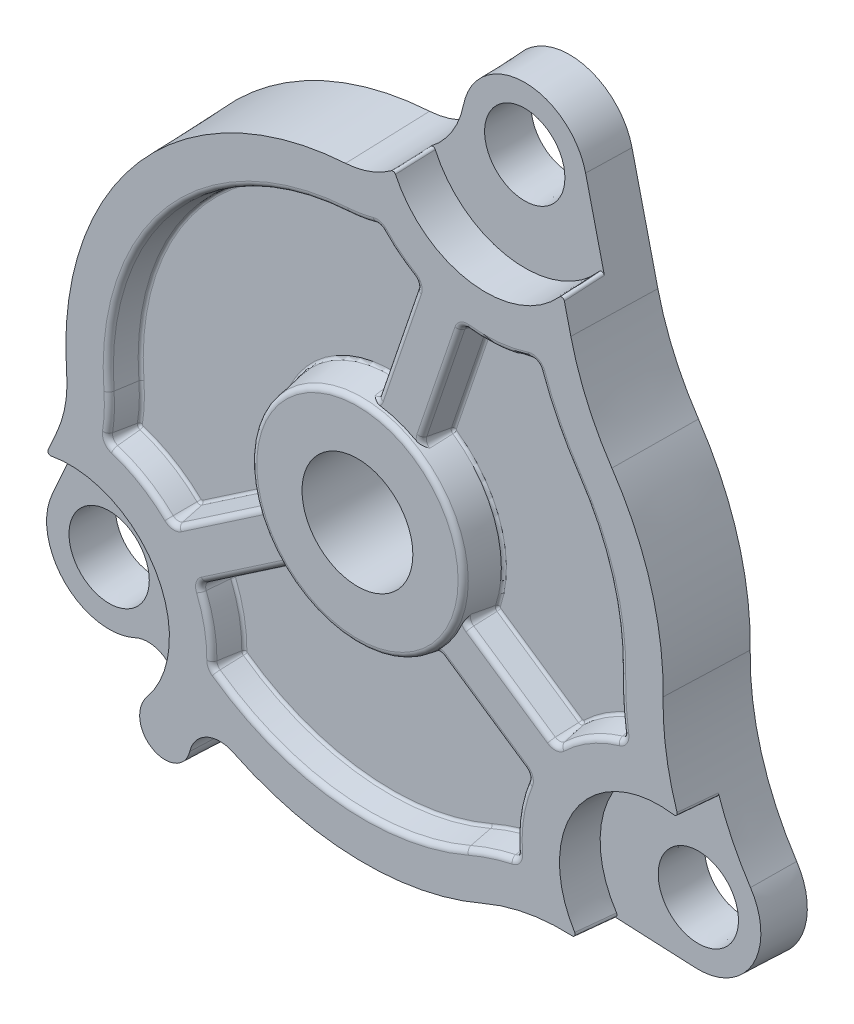
SolidWorks part; units mm, degrees
material "7075-T6 (SN)"
ref_plane "Plane1" through (0, 0, 0) normal (0, 0, 1) x (1, 0, 0)
ref_plane "Plane2" through (0, 0, 0) normal (0, 1, 0) x (-1, 0, 0)
ref_plane "Plane3" through (0, 0, 0) normal (1, 0, 0) x (0, 0, -1)
sketch "Sketch1" plane through (0, 0, 0) normal (0, 0, 1) x (1, 0, 0)
  line L0 (-26.67, -18.1463) -> (26.67, -18.1463) construction
  line L1 (0, 0) -> (-26.67, -18.1463) construction
  line L2 (0, 0) -> (26.67, -18.1463) construction
  line L3 (10.9563, 32.2244) -> (0, 0) construction
  line L4 (16.6043, 33.5606) -> (18.9435, 23.6736)
  line L6 (18.789, -23.5906) -> (26.4008, -23.944)
  line L11 (-28.0689, -6.9945) -> (-31.9746, -15.7912)
  line L12 (-18.0518, -25.6544) -> (0, 0) construction
  arc A1 (-31.9746, -15.7912) -> (-24.2263, -23.4107) centre (-26.67, -18.1463) ccw
  arc A3 (16.6043, 33.5606) -> (5.2649, 33.3618) centre (10.9563, 32.2244) ccw
  arc A4 (27.3007, -0.4835) -> (22.6196, 15.2943) centre (0, 0) ccw
  arc A5 (31.511, -14.9447) -> (27.3007, -0.4835) centre (52.6967, -0.9332) cw
  arc A6 (5.2649, 33.3618) -> (-1.7257, 27.2504) centre (-2.2073, 34.8552) cw
  arc A7 (-1.7257, 27.2504) -> (-27.2247, -2.0929) centre (0, 0) ccw
  arc A9 (26.4008, -23.944) -> (31.511, -14.9447) centre (26.67, -18.1463) ccw
  arc A10 (-11.969, -24.5419) -> (10.8798, -25.0438) centre (0, 0) ccw
  arc A12 (-27.2247, -2.0929) -> (-28.0689, -6.9945) centre (-37.3548, -2.8716) cw
  arc A13 (22.6196, 15.2943) -> (18.9435, 23.6736) centre (43.6611, 29.5216) cw
  arc A14 (18.789, -23.5906) -> (10.8798, -25.0438) centre (17.9643, -41.3514) ccw
  arc A15 (-20.617, -25.6846) -> (-15.5547, -26.2426) centre (-18.0518, -25.6544) ccw
  arc A16 (-11.969, -24.5419) -> (-15.5547, -26.2426) centre (-13.0824, -26.8249) ccw
  arc A17 (-20.617, -25.6846) -> (-24.2263, -23.4107) centre (-23.1568, -25.7146) ccw
  circle A18 centre (10.9563, 32.2244) radius 3.4925
  circle A19 centre (-26.67, -18.1463) radius 3.4925
  circle A20 centre (26.67, -18.1463) radius 3.4925
  dimension "D1" = 54.61
  dimension "D2" = 53.34
  dimension "D3" = 11.6078
  dimension "D4" = 32.258
  dimension "D8" = 10.16
  dimension "D9" = 7.62
  dimension "D10" = 25.4
  dimension "D11" = 17.78
  dimension "D14" = 2.54
  dimension "D16" = 2.5654
  dimension "D20" = 6.985
  dimension "D5" = 34.036
  dimension "D6" = 105.453
  dimension "D12" = 10.16
  dimension "D13" = 7.62
  dimension "D17" = 31.369
  dimension "D18" = 11.43
  dimension "D19" = 9.6247
extrude "Base" add sketch "Sketch1" along normal blind 4.064 draft 2
sketch "Sketch2" plane through (0, 0, 4.064) normal (0, 0, 1) x (1, 0, 0)
  line L0 (-27.9392, -7.0521) -> (-31.8449, -15.8487) construction
  line L1 (-27.9392, -7.0521) -> (-29.0636, -9.5846)
  line L2 (18.7956, -23.4488) -> (26.4074, -23.8022) construction
  line L3 (18.7956, -23.4488) -> (19.561, -23.4843)
  line L4 (16.4662, 33.528) -> (18.8054, 23.6409) construction
  line L5 (18.0441, 26.8583) -> (18.8054, 23.6409)
  arc A2 (-1.7167, 27.1088) -> (5.4041, 33.334) centre (-2.2073, 34.8552) ccw construction
  arc A3 (-1.7167, 27.1088) -> (2.7263, 28.8629) centre (-2.2073, 34.8552) ccw
  arc A4 (-1.7167, 27.1088) -> (-27.0832, -2.082) centre (0, 0) ccw construction
  arc A5 (-1.7167, 27.1088) -> (-27.0832, -2.082) centre (0, 0) ccw
  arc A6 (-27.9392, -7.0521) -> (-27.0832, -2.082) centre (-37.3548, -2.8716) ccw construction
  arc A7 (-27.9392, -7.0521) -> (-27.0832, -2.082) centre (-37.3548, -2.8716) ccw
  arc A12 (-20.4751, -25.683) -> (-15.6928, -26.21) centre (-18.0518, -25.6544) ccw construction
  arc A13 (-20.4751, -25.683) -> (-15.6928, -26.21) centre (-18.0518, -25.6544) ccw
  arc A14 (-11.9068, -24.4144) -> (-15.6928, -26.21) centre (-13.0824, -26.8249) ccw construction
  arc A15 (-11.9068, -24.4144) -> (-15.6928, -26.21) centre (-13.0824, -26.8249) ccw
  arc A16 (-11.9068, -24.4144) -> (10.8233, -24.9137) centre (0, 0) ccw construction
  arc A17 (-11.9068, -24.4144) -> (10.8233, -24.9137) centre (0, 0) ccw
  arc A18 (18.7956, -23.4488) -> (10.8233, -24.9137) centre (17.9643, -41.3514) ccw construction
  arc A19 (18.7956, -23.4488) -> (10.8233, -24.9137) centre (17.9643, -41.3514) ccw
  arc A22 (27.1588, -0.481) -> (31.3926, -15.023) centre (52.6967, -0.9332) ccw construction
  arc A23 (27.1588, -0.481) -> (28.6251, -9.474) centre (52.6967, -0.9332) ccw
  arc A24 (27.1588, -0.481) -> (22.502, 15.2148) centre (0, 0) ccw construction
  arc A25 (27.1588, -0.481) -> (22.502, 15.2148) centre (0, 0) ccw
  arc A26 (18.8054, 23.6409) -> (22.502, 15.2148) centre (43.6611, 29.5216) ccw construction
  arc A27 (18.8054, 23.6409) -> (22.502, 15.2148) centre (43.6611, 29.5216) ccw
  arc A28 (2.7263, 28.8629) -> (18.0441, 26.8583) centre (10.9563, 32.2244) ccw
  arc A29 (28.6251, -9.474) -> (19.561, -23.4843) centre (26.67, -18.1463) ccw
  arc A30 (-29.0636, -9.5846) -> (-19.8124, -23.8037) centre (-26.67, -18.1463) cw
  circle A31 centre (26.67, -18.1463) radius 3.6344 construction
  circle A32 centre (-26.67, -18.1463) radius 3.6344 construction
  circle A33 centre (10.9563, 32.2244) radius 3.6344 construction
  arc A35 (-20.4751, -25.683) -> (-19.8124, -23.8037) centre (-17.5759, -25.6488) cw
  dimension "D1" = 8.89
extrude "Ribs" add sketch "Sketch2" along normal blind 3.556 draft 2
sketch "Sketch3" plane through (0, 0, 7.62) normal (0, 0, 1) x (1, 0, 0)
  line L0 (-14.5343, -12.347) -> (-7.1513, -7.3235)
  line L2 (4.7525, 20.2904) -> (1.3055, 10.1523)
  line L3 (8.6002, 18.9822) -> (5.1532, 8.8441)
  line L5 (9.4374, -3.9635) -> (16.8205, -8.987)
  line L7 (-26.67, -18.1463) -> (0, 0) construction
  line L8 (0, 0) -> (26.67, -18.1463) construction
  line L9 (7.1513, -7.3235) -> (14.5343, -12.347)
  line L10 (-16.8205, -8.987) -> (-9.4374, -3.9635)
  line L11 (0, 0) -> (10.9563, 32.2244) construction
  arc A71 (-16.7777, -26.3073) -> (-29.7645, -5.7011) centre (-26.67, -18.1463) ccw
  arc A72 (-13.8463, -18.2571) -> (-14.8104, -13.2669) centre (-26.67, -18.1463) ccw
  arc A74 (-24.3435, -8.6486) -> (-23.1606, -1.7805) centre (-37.3548, -2.8716) ccw
  arc A75 (-23.2918, -5.0849) -> (-23.1606, -1.7805) centre (-37.3548, -2.8716) ccw
  arc A78 (-1.4681, 23.1825) -> (5.0347, 25.6708) centre (-2.2073, 34.8552) ccw
  arc A79 (-1.4681, 23.1825) -> (-23.1606, -1.7805) centre (0, 0) ccw
  arc A80 (-1.4681, 23.1825) -> (0.9185, 23.5845) centre (-2.2073, 34.8552) ccw
  arc A81 (-1.4681, 23.1825) -> (-23.1606, -1.7805) centre (0, 0) ccw
  arc A86 (-0.8244, 27.1572) -> (20.9528, 24.1914) centre (10.9563, 32.2244) ccw
  arc A87 (1.6737, 23.376) -> (4.4195, 21.1912) centre (10.9563, 32.2244) ccw
  arc A91 (23.2253, -0.4113) -> (24.8334, -10.5496) centre (52.6967, -0.9332) ccw
  arc A92 (23.2253, -0.4113) -> (19.2429, 13.0112) centre (0, 0) ccw
  arc A93 (14.9769, 22.7351) -> (19.2429, 13.0112) centre (43.6611, 29.5216) ccw
  arc A94 (23.2253, -0.4113) -> (23.5069, -5.0313) centre (52.6967, -0.9332) ccw
  arc A95 (23.2253, -0.4113) -> (19.2429, 13.0112) centre (0, 0) ccw
  arc A96 (15.9142, 19.5741) -> (19.2429, 13.0112) centre (43.6611, 29.5216) ccw
  arc A98 (29.1809, -5.5704) -> (16.1967, -25.547) centre (26.67, -18.1463) ccw
  arc A99 (22.972, -5.8669) -> (17.7775, -8.906) centre (26.67, -18.1463) ccw
  arc A109 (18.9781, -19.5189) -> (9.2557, -21.3053) centre (17.9643, -41.3514) ccw
  arc A110 (-10.1822, -20.8783) -> (9.2557, -21.3053) centre (0, 0) ccw
  arc A111 (13.2921, -20.0006) -> (9.2557, -21.3053) centre (17.9643, -41.3514) ccw
  arc A112 (-13.5281, -18.8831) -> (9.2557, -21.3053) centre (0, 0) ccw
  arc A113 (0.5414, 9.6368) -> (-9.1442, -3.0896) centre (0, 0) ccw
  arc A114 (9.4133, 19.4933) -> (14.9591, 20.0409) centre (10.9563, 32.2244) ccw
  arc A115 (14.8104, -13.2669) -> (13.8887, -19.1939) centre (26.67, -18.1463) ccw
  arc A116 (-17.7775, -8.906) -> (-22.7707, -5.9293) centre (-26.67, -18.1463) ccw
  arc A117 (9.1442, -3.0896) -> (5.4448, 7.9696) centre (0, 0) ccw
  arc A118 (-6.2307, -7.3715) -> (6.2307, -7.3715) centre (0, 0) ccw
  arc A119 (1.6737, 23.376) -> (0.9185, 23.5845) centre (1.1222, 22.8502) ccw
  arc A120 (4.7525, 20.2904) -> (4.4195, 21.1912) centre (4.031, 20.5357) ccw
  arc A121 (8.6002, 18.9822) -> (9.4133, 19.4933) centre (9.3216, 18.7369) cw
  arc A122 (15.9142, 19.5741) -> (14.9591, 20.0409) centre (15.1969, 19.317) ccw
  arc A123 (23.5069, -5.0313) -> (22.972, -5.8669) centre (22.7523, -5.1373) cw
  arc A124 (-22.7707, -5.9293) -> (-23.2918, -5.0849) centre (-22.5391, -5.2034) cw
  arc A125 (5.4448, 7.9696) -> (5.1532, 8.8441) centre (5.8747, 8.5988) cw
  arc A126 (1.3055, 10.1523) -> (0.5414, 9.6368) centre (0.5841, 10.3976) cw
  arc A127 (17.7775, -8.906) -> (16.8205, -8.987) centre (17.2492, -8.357) cw
  arc A128 (14.8104, -13.2669) -> (14.5343, -12.347) centre (14.1057, -12.977) ccw
  arc A129 (9.1442, -3.0896) -> (9.4374, -3.9635) centre (9.8661, -3.3335) ccw
  arc A130 (7.1513, -7.3235) -> (6.2307, -7.3715) centre (6.7226, -7.9535) ccw
  arc A131 (13.8887, -19.1939) -> (13.2921, -20.0006) centre (13.1292, -19.2562) cw
  arc A132 (-13.8463, -18.2571) -> (-13.5281, -18.8831) centre (-13.0843, -18.2637) ccw
  arc A133 (-9.4374, -3.9635) -> (-9.1442, -3.0896) centre (-9.8661, -3.3335) ccw
  arc A134 (-17.7775, -8.906) -> (-16.8205, -8.987) centre (-17.2492, -8.357) ccw
  arc A135 (-6.2307, -7.3715) -> (-7.1513, -7.3235) centre (-6.7226, -7.9535) ccw
  arc A136 (-14.5343, -12.347) -> (-14.8104, -13.2669) centre (-14.1057, -12.977) ccw
  dimension "D7" = 19.304
  dimension "D12" = 0.762
  dimension "D9" = 4.064
  dimension "D10" = 4.064
  dimension "D11" = 4.064
  dimension "D1" = 3.81
  dimension "D2" = 3.81
  dimension "D3" = 3.81
  dimension "D4" = 3.81
  dimension "D5" = 3.81
  dimension "D6" = 3.81
  dimension "D8" = 3.81
extrude "Rib Cut" cut sketch "Sketch3" against normal blind 2.54 draft 10
sketch "Sketch4" plane through (0, 0, 7.62) normal (0, 0, 1) x (1, 0, 0)
  circle A0 centre (0, 0) radius 9.652
  arc A1 (9.1442, -3.0896) -> (5.4448, 7.9696) centre (0, 0) ccw construction
extrude "Shaft Boss" add sketch "Sketch4" along normal blind 0.635 draft 10
sketch "Sketch5" plane through (0, 0, 8.255) normal (0, 0, 1) x (1, 0, 0)
  circle A0 centre (0, 0) radius 5.0165
  circle A1 centre (0, 0) radius 9.54 construction
  dimension "D1" = 10.033
extrude "Shaft Bore" cut sketch "Sketch5" against normal through all
fillet "Fillet1" radius 0.508 39 edges at (-0.2644, 23.3216, 7.62) (2.9715, 22.1893, 7.62) (3.029, 15.2213, 7.62) (1.0102, 9.7659, 7.62) (-20.1033, -7.131, 7.62) (-23.1875, -5.6036, 7.62) (-23.1299, -3.4365, 7.62) (-17.5337, 15.2365, 7.62) (-17.3134, -9.1163, 7.62) (-13.129, -6.4752, 7.62) (-9.1437, -3.5759, 7.62) (4.7458, 20.7999, 7.62) (1.325, 23.5847, 7.62) (23.2753, -2.7268, 7.62) (23.3941, -5.5481, 7.62) (20.194, -7.0774, 7.62) (17.3134, -9.1163, 7.62) (5.1518, 8.3578, 7.62) (8.9161, 19.382, 7.62) (12.2163, 19.4622, 7.62) (17.373, 16.1884, 7.62) (22.2694, 6.6071, 7.62) (15.5315, 20.0016, 7.62) (6.8767, 13.9131, 7.62) (9.1437, -3.5759, 7.62) (13.129, -6.4752, 7.62) (-14.0786, -15.7138, 7.62) (-10.8428, -9.8352, 7.62) (10.8428, -9.8352, 7.62) (13.9981, -16.1758, 7.62) (13.7419, -19.7093, 7.62) (11.2422, -20.5548, 7.62) (-2.4556, -23.0987, 7.62) (14.8355, -12.758, 7.62) (6.6829, -7.1925, 7.62) (-6.6829, -7.1925, 7.62) (-14.8355, -12.758, 7.62) (-13.7636, -18.609, 7.62) (9.54, 0, 8.255)
fillet "Fillet2" radius 0.254 41 edges at (-17.1956, 14.9428, 5.08) (1.2058, 23.153, 5.08) (4.3257, 20.6446, 5.08) (-9.5683, -3.4334, 5.08) (-13.3809, -6.1049, 5.08) (-17.2756, -8.67, 5.08) (-0.19, 22.8799, 5.08) (2.6927, 21.8388, 5.08) (2.605, 15.3655, 5.08) (0.7598, 10.1372, 5.08) (-8.037, 6.1167, 5.08) (-19.8739, -6.7463, 5.08) (-22.8064, -5.3684, 5.08) (-22.6824, -3.4543, 5.08) (21.8401, 6.4797, 5.08) (13.3809, -6.1049, 5.08) (9.5683, -3.4334, 5.08) (7.3007, 13.769, 5.08) (15.3349, 19.5992, 5.08) (22.8282, -2.7541, 5.08) (23.0169, -5.3066, 5.08) (19.9678, -6.6909, 5.08) (17.2756, -8.67, 5.08) (9.5782, 3.2039, 5.08) (5.5767, 8.4994, 5.08) (9.1544, 19.0028, 5.08) (12.2603, 19.0165, 5.08) (16.9736, 15.9858, 5.08) (-2.4083, -22.6534, 5.08) (-13.3644, -18.406, 5.08) (-14.4066, -12.8867, 5.08) (-6.7062, -7.6398, 5.08) (6.7062, -7.6398, 5.08) (14.4066, -12.8867, 5.08) (-13.6389, -15.6288, 5.08) (-10.5909, -10.2055, 5.08) (0, -10.0999, 5.08) (10.5909, -10.2055, 5.08) (13.5556, -16.1069, 5.08) (13.3818, -19.443, 5.08) (11.1044, -20.1286, 5.08)
fillet "Fillet3" radius 0.254 8 edges
sketch "Sketch6" plane through (0, 0, 0) normal (0, 0, -1) x (-1, 0, 0)
  circle A0 centre (0, 0) radius 23.5
  circle A1 centre (0, 0) radius 5.0165 construction
  circle A2 centre (0, 0) radius 5.0165
  dimension "D1" = 47
extrude "Boss-Extrude1" add sketch "Sketch6" along normal blind 1
